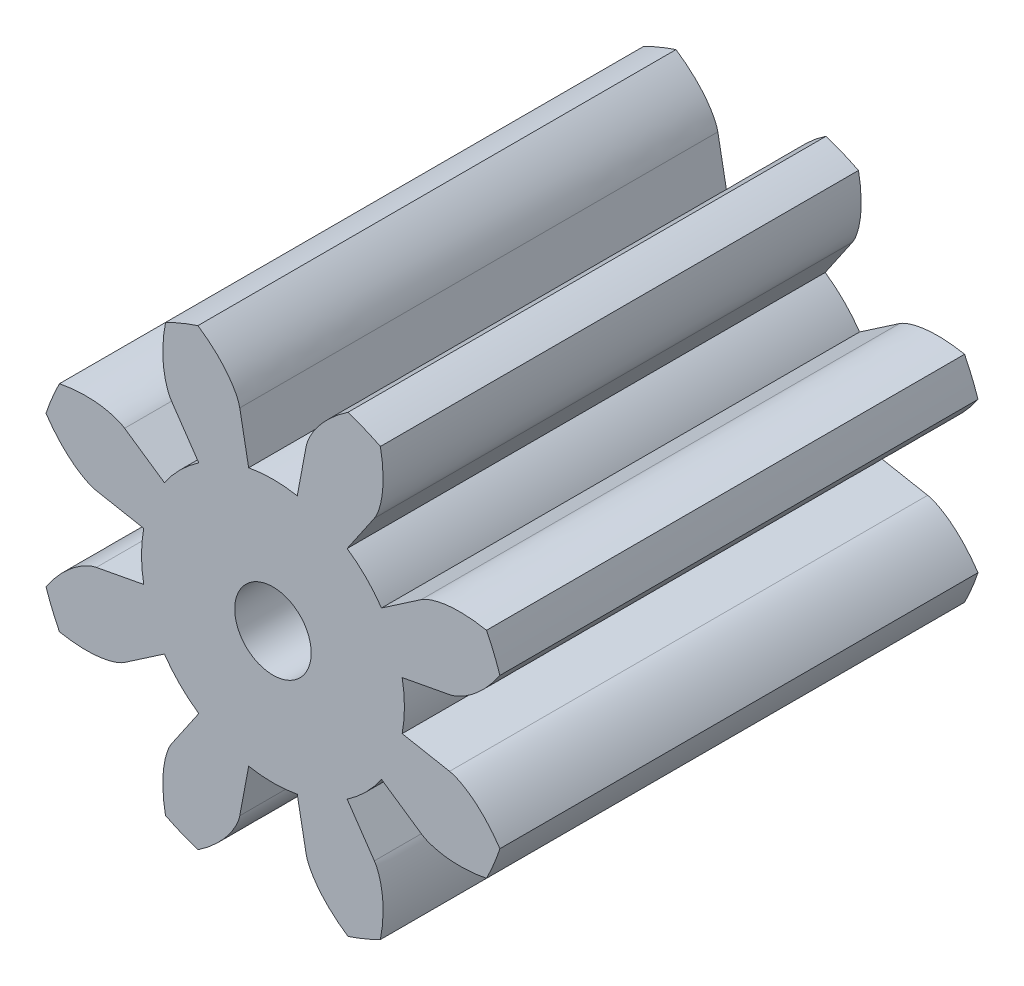
SolidWorks part; units mm, degrees
ref_plane "前视基准面" through (0, 0, 0) normal (0, 0, 1) x (1, 0, 0)
ref_plane "上视基准面" through (0, 0, 0) normal (0, 1, 0) x (1, 0, 0)
ref_plane "右视基准面" through (0, 0, 0) normal (1, 0, 0) x (0, 0, -1)
other "Configuration Table"
sketch "草图1" plane through (0, 0, 0) normal (0, 0, 1) x (1, 0, 0)
  line L0 (0, 0) -> (2, 0) construction
  line L1 (0, 0) -> (1.9616, 0.3902) construction
  line L2 (0, 0) -> (1.847, 0.3472)
  line L3 (1.9616, 0.3902) -> (1.9616, -0.3902) construction
  line L4 (0, 0) -> (1.847, -0.3472)
  circle A0 centre (0, 0) radius 2.5
  circle A1 centre (0, 0) radius 2 construction
  circle A2 centre (0, 0) radius 1.375
  circle A3 centre (0, 0) radius 1.8794 construction
  circle A4 centre (0, 0) radius 0.4
  spline S0 degree 4 poles (1.847, 0.3472) (1.8611, 0.3499) (1.8998, 0.3602) (1.9702, 0.3913) (2.0761, 0.4569) (2.1988, 0.5623) (2.3355, 0.7185) (2.4665, 0.9238) (2.5766, 1.1675) (2.6577, 1.444) (2.7041, 1.7282) (2.7181, 2.0157) (2.7012, 2.3172) (2.6413, 2.6864) (2.5141, 3.1146) (2.295, 3.5854) (1.974, 4.0645) (1.5873, 4.4921) (1.1471, 4.8637) (0.6624, 5.1758) (0.1448, 5.4269) (-0.4003, 5.616) (-0.8893, 5.728) (-1.3203, 5.7854) (-1.6732, 5.8093) (-1.9718, 5.8119) (-2.2122, 5.8048) (-2.4961, 5.7806) (-2.6802, 5.7582) (-2.941, 5.7188) (-3.1347, 5.6778) (-3.3298, 5.6345) (-3.426, 5.6067) (-3.4888, 5.5904) knots 0 0 0 0 0 0.005604 0.015718 0.02996 0.048734 0.068727 0.096889 0.125051 0.153212 0.181374 0.209535 0.237696 0.271429 0.327752 0.384075 0.440398 0.496721 0.553044 0.609367 0.66569 0.722013 0.778336 0.806497 0.834659 0.86282 0.890982 0.909091 0.931818 0.954545 0.977273 1 1 1 1 1 construction
  spline S1 degree 4 poles (1.847, 0.3472) (1.8611, 0.3499) (1.8998, 0.3602) (1.9702, 0.3913) (2.0761, 0.4569) (2.1988, 0.5623) (2.3355, 0.7185) (2.4665, 0.9238) (2.5766, 1.1675) (2.6577, 1.444) (2.7041, 1.7282) (2.7181, 2.0157) (2.7012, 2.3172) (2.6413, 2.6864) (2.5141, 3.1146) (2.295, 3.5854) (1.974, 4.0645) (1.5873, 4.4921) (1.1471, 4.8637) (0.6624, 5.1758) (0.1448, 5.4269) (-0.4003, 5.616) (-0.8893, 5.728) (-1.3203, 5.7854) (-1.6732, 5.8093) (-1.9718, 5.8119) (-2.2122, 5.8048) (-2.4297, 5.7863) (-2.5365, 5.7749) (-2.5782, 5.77) knots 0 0 0 0 0 0.005604 0.015718 0.02996 0.048734 0.068727 0.096889 0.125051 0.153212 0.181374 0.209535 0.237696 0.271429 0.327752 0.384075 0.440398 0.496721 0.553044 0.609367 0.66569 0.722013 0.778336 0.806497 0.834659 0.86282 0.890982 0.909091 0.909091 0.909091 0.909091 0.909091
  spline S2 degree 4 poles (1.847, -0.3472) (1.8611, -0.3499) (1.8998, -0.3602) (1.9702, -0.3913) (2.0761, -0.4569) (2.1988, -0.5623) (2.3355, -0.7185) (2.4665, -0.9238) (2.5766, -1.1675) (2.6577, -1.444) (2.7041, -1.7282) (2.7181, -2.0157) (2.7012, -2.3172) (2.6413, -2.6864) (2.5141, -3.1146) (2.295, -3.5854) (1.974, -4.0645) (1.5873, -4.4921) (1.1471, -4.8637) (0.6624, -5.1758) (0.1448, -5.4269) (-0.4003, -5.616) (-0.8893, -5.728) (-1.3203, -5.7854) (-1.6732, -5.8093) (-1.9718, -5.8119) (-2.2122, -5.8048) (-2.4961, -5.7806) (-2.6802, -5.7582) (-2.941, -5.7188) (-3.1347, -5.6778) (-3.3298, -5.6345) (-3.426, -5.6067) (-3.4888, -5.5904) knots 0 0 0 0 0 0.005604 0.015718 0.02996 0.048734 0.068727 0.096889 0.125051 0.153212 0.181374 0.209535 0.237696 0.271429 0.327752 0.384075 0.440398 0.496721 0.553044 0.609367 0.66569 0.722013 0.778336 0.806497 0.834659 0.86282 0.890982 0.909091 0.931818 0.954545 0.977273 1 1 1 1 1 construction
  spline S3 degree 4 poles (1.847, -0.3472) (1.8611, -0.3499) (1.8998, -0.3602) (1.9702, -0.3913) (2.0761, -0.4569) (2.1988, -0.5623) (2.3355, -0.7185) (2.4665, -0.9238) (2.5766, -1.1675) (2.6577, -1.444) (2.7041, -1.7282) (2.7181, -2.0157) (2.7012, -2.3172) (2.6413, -2.6864) (2.5141, -3.1146) (2.295, -3.5854) (1.974, -4.0645) (1.5873, -4.4921) (1.1471, -4.8637) (0.6624, -5.1758) (0.1448, -5.4269) (-0.4003, -5.616) (-0.8893, -5.728) (-1.3203, -5.7854) (-1.6732, -5.8093) (-1.9718, -5.8119) (-2.2122, -5.8048) (-2.4297, -5.7863) (-2.5365, -5.7749) (-2.5782, -5.77) knots 0 0 0 0 0 0.005604 0.015718 0.02996 0.048734 0.068727 0.096889 0.125051 0.153212 0.181374 0.209535 0.237696 0.271429 0.327752 0.384075 0.440398 0.496721 0.553044 0.609367 0.66569 0.722013 0.778336 0.806497 0.834659 0.86282 0.890982 0.909091 0.909091 0.909091 0.909091 0.909091
  point P15 (1.9616, 0)
  dimension "齿顶圆直径" = 5
  dimension "分度圆直径" = 4
  dimension "齿根圆直径" = 2.75
  dimension "基圆直径" = 3.7588
  dimension "内孔直径" = 0.8
  dimension "渐近线镜像线夹角" = 11.25
extrude "凸台-拉伸1" add sketch "草图1" along normal blind 5 contours A0 | A4
extrude "切除-拉伸1" cut sketch "草图1<3>" along normal through all contours A2 S3 A0 S1 region at (2.0267, 0, 0)
sketch "草图1<3>" plane through (0, 0, 0) normal (0, 0, 1) x (1, 0, 0) same geometry as "草图1"
pattern_circular "阵列(圆周)1" count 8 every 45 about axis through (0, 0, 5) along (0, 0, 1) of "切除-拉伸1"
equation "\"m\"= 0.5'模数"
equation "\"z\"= 8'齿数"
equation "\"a\"= 20度'压力角"
equation "\"d\"= \"m\" * \"z\"'分度圆直径"
equation "\"da\"= ( \"z\" + 2 ) * \"m\"'齿顶圆直径"
equation "\"df\"= ( \"z\" - 2.5 ) * \"m\"'齿根圆直径"
equation "\"s\"= 0.5 * PI * \"m\"'分度圆齿厚"
equation "\"r\"= 0.38 * \"m\"'齿根圆角"
equation "\"B\"= 0.3 * \"d\"'齿厚"
equation "\"db\"= \"m\" * \"z\" * cos ( \"a\" )'基圆直径"
equation "\"rb\"= \"db\" / 2'基圆半径"
equation "\"齿顶圆直径@草图1\"= \"da\""
equation "\"分度圆直径@草图1\"= \"d\""
equation "\"齿根圆直径@草图1\"= \"df\""
equation "\"基圆直径@草图1\"= \"db\""
equation "\"渐近线镜像线夹角@草图1\"= 360 / 4 / \"z\""
equation "\"h\"= 5'齿轮厚度"
equation "\"ir\" = 0.8'内孔直径"
equation "\"内孔直径@草图1\"= \"ir\""
equation "\"齿轮厚@凸台-拉伸1\"= \"h\""
equation "\"齿轮夹角@阵列(圆周)1\"= 360 / \"z\""
equation "\"齿数@阵列(圆周)1\"= \"z\""
